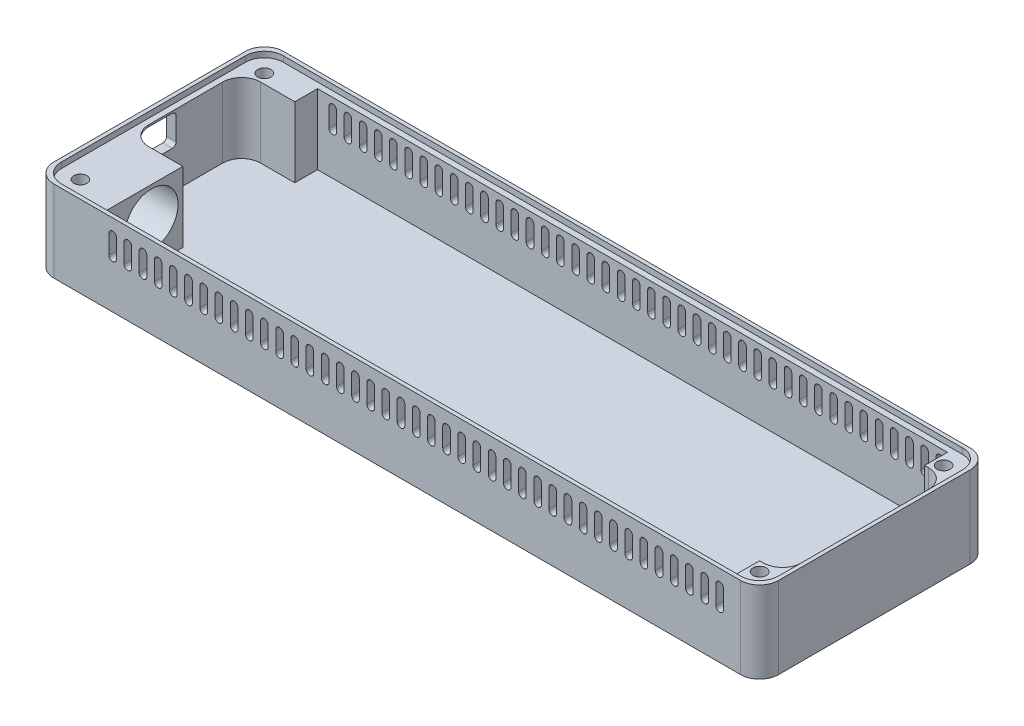
SolidWorks part; units mm, degrees
ref_plane "Front Plane" through (0, 0, 0) normal (0, 0, 1) x (1, 0, 0)
ref_plane "Top Plane" through (0, 0, 0) normal (0, 1, 0) x (1, 0, 0)
ref_plane "Right Plane" through (0, 0, 0) normal (1, 0, 0) x (0, 0, -1)
sketch "Sketch1" plane through (0, 0, 0) normal (0, 1, 0) x (1, 0, 0)
  line L0 (-100.5, 30.25) -> (90.5, 30.25)
  line L1 (82.5, -27.75) -> (-82.5, -27.75)
  line L2 (82.5, -27.75) -> (82.5, 27.75)
  line L3 (82.5, 27.75) -> (-82.5, 27.75)
  line L4 (-82.5, -27.75) -> (-82.5, 27.75)
  line L5 (82.5, -27.75) -> (-82.5, 27.75) construction
  line L6 (82.5, 27.75) -> (-82.5, -27.75) construction
  line L7 (90.5, 30.25) -> (90.5, -30.25)
  line L8 (90.5, -30.25) -> (-100.5, -30.25)
  line L9 (-100.5, -30.25) -> (-100.5, 30.25)
  line L10 (82.5, 30.25) -> (82.5, 27.75) construction
  point P0 (0, 0)
  point P10 (90.5, 0)
  dimension "D1" = 55.5
  dimension "D2" = 165
  dimension "D3" = 2.5
  dimension "D4" = 8
  dimension "D5" = 18
extrude "Boss-Extrude1" add sketch "Sketch1" along normal blind 1.5 contours L4 L1 L2 L3 | L9 L8 L7 L0 L1 L4 L3 L2 | L2 L1 L4 L3 | L9 L0 L7 L8 region at (-5, 0, -28.2465) region at (0, 0, 0)
sketch "Sketch2" plane through (0, 1.5, 0) normal (0, 1, 0) x (1, 0, 0)
  line L4 (-100.5, 30.25) -> (-100.5, -30.25)
  line L5 (-100.5, -30.25) -> (90.5, -30.25)
  line L6 (90.5, -30.25) -> (90.5, 30.25)
  line L7 (90.5, 30.25) -> (-100.5, 30.25)
  line L8 (-100.5, 30.25) -> (-100.5, -30.25)
  line L9 (-100.5, -30.25) -> (90.5, -30.25)
  line L10 (90.5, -30.25) -> (90.5, 30.25)
  line L11 (90.5, 30.25) -> (-100.5, 30.25)
  dimension "D1" = 0
extrude "Extrude-Thin1" add sketch "Sketch2" along normal blind 20 thin thin type one direction reverse wall 2.5
sketch "Sketch5" plane through (0, 1.5, 0) normal (0, 1, 0) x (1, 0, 0)
  line L0 (-98, 27.75) -> (-98, -27.75) construction
  line L1 (-98, 27.75) -> (-84, 27.75)
  line L2 (-98, 27.75) -> (-98, 21.75)
  line L3 (-98, 21.75) -> (-84, 21.75)
  line L4 (-84, 27.75) -> (-84, 21.75)
  line L5 (88, 27.75) -> (82, 27.75)
  line L6 (88, 27.75) -> (88, 21.75)
  line L7 (88, 21.75) -> (82, 21.75)
  line L8 (82, 27.75) -> (82, 21.75)
  line L9 (88, -27.75) -> (82, -27.75)
  line L10 (88, -27.75) -> (88, -21.75)
  line L11 (88, -21.75) -> (82, -21.75)
  line L12 (82, -27.75) -> (82, -21.75)
  line L13 (-98, -27.75) -> (-84, -27.75)
  line L14 (-98, -27.75) -> (-98, -7.75)
  line L15 (-98, -7.75) -> (-84, -7.75)
  line L16 (-84, -27.75) -> (-84, -7.75)
  dimension "D1" = 166
  dimension "D2" = 6
  dimension "D3" = 6
  dimension "D4" = 20
extrude "Boss-Extrude2" add sketch "Sketch5" along normal through all
sketch "Sketch10" plane through (-100.5, 0, 0) normal (-1, 0, 0) x (0, 0, 1)
  circle A0 centre (16, 12) radius 5.1
  dimension "D1" = 10.2
  dimension "D2" = 12
  dimension "D3" = 16
extrude "Cut-Extrude5" cut sketch "Sketch10" against normal blind 4
sketch "Sketch3" plane through (-96.5, 0, 0) normal (-1, 0, 0) x (0, 0, 1)
  line L0 (19.5, 13.9365) -> (19.5, 10.0635)
  line L1 (12.5, 13.9365) -> (12.5, 10.0635)
  arc A0 (19.5, 13.9365) -> (12.5, 13.9365) centre (16, 12) ccw
  arc A1 (12.5, 10.0635) -> (19.5, 10.0635) centre (16, 12) ccw
  dimension "D1" = 4
  dimension "D2" = 7
extrude "Cut-Extrude1" cut sketch "Sketch3" against normal up to next
sketch "Sketch11" plane through (-84, 0, 0) normal (1, 0, 0) x (0, 0, -1)
  circle A0 centre (-16, 12) radius 7
  dimension "D1" = 14
extrude "Cut-Extrude7" cut sketch "Sketch11" against normal offset from surface (10 mm away) 2.5 up to face at (-96.5, 12, 16)
sketch "Sketch4" plane through (-100.5, 0, 0) normal (-1, 0, 0) x (0, 0, 1)
  line L1 (-4.5, 19.5) -> (7.5, 19.5)
  line L2 (-4.5, 19.5) -> (-4.5, 11.5)
  line L3 (-4.5, 11.5) -> (7.5, 11.5)
  line L4 (7.5, 19.5) -> (7.5, 11.5)
  line L5 (-21.75, 1.5) -> (7.75, 1.5) construction
  point P4 (6.6861, 10)
  point P5 (1.5, 11.5)
  point P10 (-4.5, 15.5)
  dimension "D1" = 12
  dimension "D2" = 8
  dimension "D3" = 14
  dimension "D4" = 1.5
extrude "Cut-Extrude2" cut sketch "Sketch4" against normal up to next
sketch "Sketch6" plane through (0, 21.5, 0) normal (0, 1, 0) x (1, 0, 0)
  line L0 (89.5, 29.25) -> (-99.5, 29.25)
  line L1 (-99.5, 29.25) -> (-99.5, -29.25)
  line L2 (-99.5, -29.25) -> (89.5, -29.25)
  line L3 (89.5, -29.25) -> (89.5, 29.25)
  line L4 (90.5, 30.25) -> (-100.5, 30.25)
  line L5 (-100.5, 30.25) -> (-100.5, -30.25)
  line L6 (-100.5, -30.25) -> (90.5, -30.25)
  line L7 (90.5, -30.25) -> (90.5, 30.25)
  line L8 (90.5, 30.25) -> (-100.5, 30.25) construction
  line L9 (-100.5, 30.25) -> (-100.5, -30.25) construction
  line L10 (-100.5, -30.25) -> (90.5, -30.25) construction
  line L11 (90.5, -30.25) -> (90.5, 30.25) construction
  dimension "D1" = 0
  dimension "D2" = 1
extrude "Cut-Extrude3" cut sketch "Sketch6" against normal blind 1.5
fillet "Fillet1" radius 5 4 edges at (88, 10.75, -21.75) (88, 10.75, 21.75) (-98, 10.75, 7.75) (-98, 10.75, -21.75)
fillet "Fillet2" radius 5 4 edges at (89.5, 20.75, -29.25) (-99.5, 20.75, 29.25) (89.5, 20.75, 29.25) (-99.5, 20.75, -29.25)
fillet "Fillet3" radius 5 4 edges at (90.5, 10.75, -30.25) (-100.5, 10.75, 30.25) (-100.5, 10.75, -30.25) (90.5, 10.75, 30.25)
hole_wizard "Hole1" positions "Sketch7" profile "Sketch8" legacy
sketch "Sketch7" plane through (0, 20, 0) normal (0, 1, 0) x (1, 0, 0)
  point P0 (-94.5, 24.25)
  point P2 (-94.5, -24.25)
  point P4 (84.5, -24.25)
  point P7 (84.5, 24.25)
sketch "Sketch8" plane through (-94.5, 20, -24.25) normal (1, 0, 0) x (0, 0, 1)
  line L0 (0, 0) -> (0, 6)
  line L1 (0, 6) -> (1.25, 6)
  line L2 (1.25, 6) -> (1.25, 2.95)
  line L3 (1.25, 2.95) -> (1.75, 2.95)
  line L4 (1.75, 2.95) -> (1.75, 0)
  line L5 (1.75, 0) -> (0, 0)
  line L6 (0, 110) -> (0, -10) construction
  dimension "Diameter" = 2.5
  dimension "Depth" = 6
  dimension "C-Bore Diameter" = 3.5
  dimension "C-Bore Depth" = 2.95
sketch "Sketch9" plane through (0, 0, 30.25) normal (0, 0, 1) x (1, 0, 0)
  line L0 (0, 12.5) -> (0, 17.5) construction
  line L1 (-1, 12.5) -> (-1, 17.5)
  line L2 (1, 12.5) -> (1, 17.5)
  line L3 (-95.5, 21.5) -> (85.5, 21.5) construction
  arc A0 (-1, 12.5) -> (1, 12.5) centre (0, 12.5) ccw
  arc A1 (1, 17.5) -> (-1, 17.5) centre (0, 17.5) ccw
  point P3 (0, 15)
  dimension "D1" = 2
  dimension "D2" = 5
  dimension "D3" = 4
extrude "Cut-Extrude4" cut sketch "Sketch9" against normal through all
pattern_linear "LPattern1" count 21 spacing 4 along (-1, 0, 0) of "Cut-Extrude4"
pattern_linear "LPattern2" count 21 spacing 4 along (1, 0, 0) of "Cut-Extrude4"
fillet "Fillet4" radius 1 4 edges at (-97.5306, 11.5, 7.5) (-97.5306, 19.5, 7.5) (-99.25, 19.5, -4.5) (-99.25, 11.5, -4.5)
